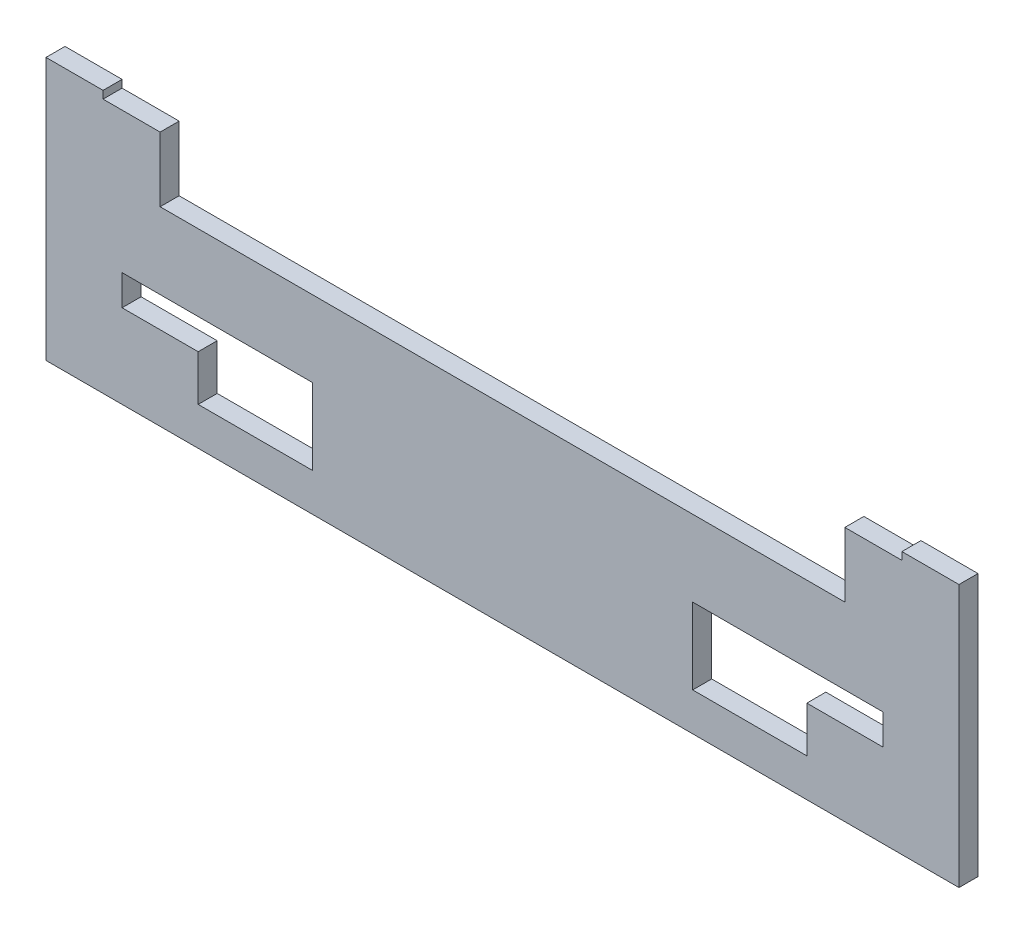
SolidWorks part; units mm, degrees
material "Acrylic (Medium-high impact)"
ref_plane "Front Plane" through (0, 0, 0) normal (0, 0, 1) x (1, 0, 0)
ref_plane "Top Plane" through (0, 0, 0) normal (0, 1, 0) x (1, 0, 0)
ref_plane "Right Plane" through (0, 0, 0) normal (1, 0, 0) x (0, 0, -1)
sketch "Sketch1" plane through (0, 0, 0) normal (0, 0, 1) x (1, 0, 0)
  line L0 (0, 0) -> (240, 0)
  line L3 (240, 0) -> (240, 69)
  line L6 (240, 69) -> (225, 69)
  line L7 (225, 69) -> (225, 67)
  line L8 (225, 67) -> (210, 67)
  line L9 (210, 67) -> (210, 50)
  line L10 (210, 50) -> (30, 50)
  line L11 (30, 50) -> (30, 67)
  line L12 (30, 67) -> (15, 67)
  line L13 (15, 67) -> (15, 69)
  line L14 (15, 69) -> (0, 69)
  line L17 (0, 69) -> (0, 0)
  dimension "D1" = 30
  dimension "D2" = 30
  dimension "D3" = 180
  dimension "D4" = 15
  dimension "D5" = 2
  dimension "D6" = 17
  dimension "D7" = 50
extrude "Boss-Extrude1" add sketch "Sketch1" along normal blind 5
sketch "Sketch6" plane through (0, 0, 5) normal (0, 0, 1) x (1, 0, 0)
  line L0 (20, 30) -> (70, 30)
  line L1 (70, 30) -> (70, 10)
  line L2 (70, 10) -> (40, 10)
  line L3 (40, 10) -> (40, 22)
  line L4 (40, 22) -> (20, 22)
  line L5 (20, 22) -> (20, 30)
  line L6 (0, 0) -> (240, 0) construction
  line L7 (0, 69) -> (0, 0) construction
  line L8 (120, 0) -> (120, 50) construction
  line L9 (210, 50) -> (30, 50) construction
  line L10 (220, 22) -> (220, 30)
  line L11 (200, 22) -> (220, 22)
  line L12 (200, 10) -> (200, 22)
  line L13 (170, 10) -> (200, 10)
  line L14 (170, 30) -> (170, 10)
  line L15 (220, 30) -> (170, 30)
  dimension "D1" = 50
  dimension "D2" = 20
  dimension "D3" = 8
  dimension "D4" = 12
  dimension "D5" = 10
  dimension "D6" = 20
extrude "Cut-Extrude5" cut sketch "Sketch6" against normal up to next
